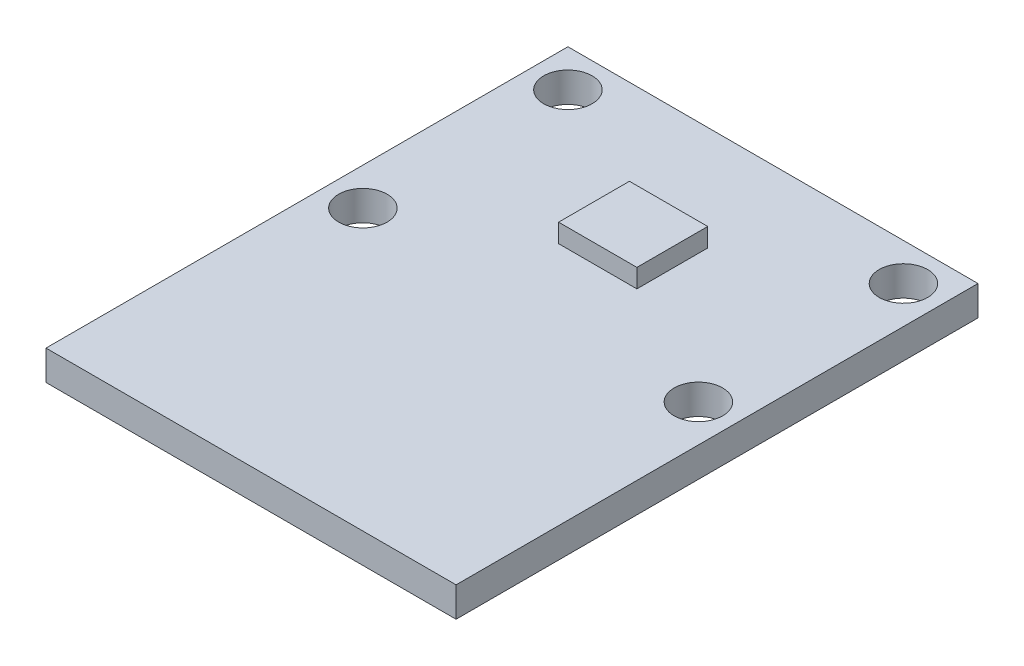
SolidWorks part; units mm, degrees
ref_plane "Front Plane" through (0, 0, 0) normal (0, 0, 1) x (1, 0, 0)
ref_plane "Top Plane" through (0, 0, 0) normal (0, 1, 0) x (1, 0, 0)
ref_plane "Right Plane" through (0, 0, 0) normal (1, 0, 0) x (0, 0, -1)
sketch "Sketch1" plane through (0, 0, 0) normal (0, 1, 0) x (1, 0, 0)
  line L0 (0, 7.5) -> (0, 5.5) construction
  line L1 (-9, 5.5) -> (9, 5.5) construction
  line L2 (-9, 5.5) -> (-9, -5.5) construction
  line L3 (-9, -5.5) -> (9, -5.5) construction
  line L4 (9, 5.5) -> (9, -5.5) construction
  line L5 (-9, 5.5) -> (9, -5.5) construction
  line L6 (-9, -5.5) -> (9, 5.5) construction
  line L7 (-11, 7.5) -> (11, 7.5)
  line L8 (-11, 7.5) -> (-11, -20.5)
  line L9 (-11, -20.5) -> (11, -20.5)
  line L10 (11, 7.5) -> (11, -20.5)
  line L11 (-11, 5.5) -> (-9, 5.5) construction
  circle A0 centre (9, 5.5) radius 1.3
  circle A1 centre (-9, 5.5) radius 1.3
  circle A2 centre (-9, -5.5) radius 1.3
  circle A3 centre (9, -5.5) radius 1.3
  point P0 (0, 0)
  dimension "D5" = 2.6
  dimension "D1" = 11
  dimension "D2" = 18
  dimension "D3" = 22
  dimension "D4" = 28
extrude "Boss-Extrude1" add sketch "Sketch1" along normal blind 1.6
ref_axis "Axis1" through (0, 0, 0) along (0, 1, 0)
sketch "Sketch2" plane through (0, 1.6, 0) normal (0, 1, 0) x (1, 0, 0)
  line L1 (2.1, -1.9) -> (-2.1, -1.9)
  line L2 (2.1, -1.9) -> (2.1, 1.9)
  line L3 (2.1, 1.9) -> (-2.1, 1.9)
  line L4 (-2.1, -1.9) -> (-2.1, 1.9)
  line L5 (2.1, -1.9) -> (-2.1, 1.9) construction
  line L6 (2.1, 1.9) -> (-2.1, -1.9) construction
  point P0 (0, 0)
  dimension "D1" = 4.2
  dimension "D2" = 3.8
extrude "Boss-Extrude2" add sketch "Sketch2" along normal blind 1
